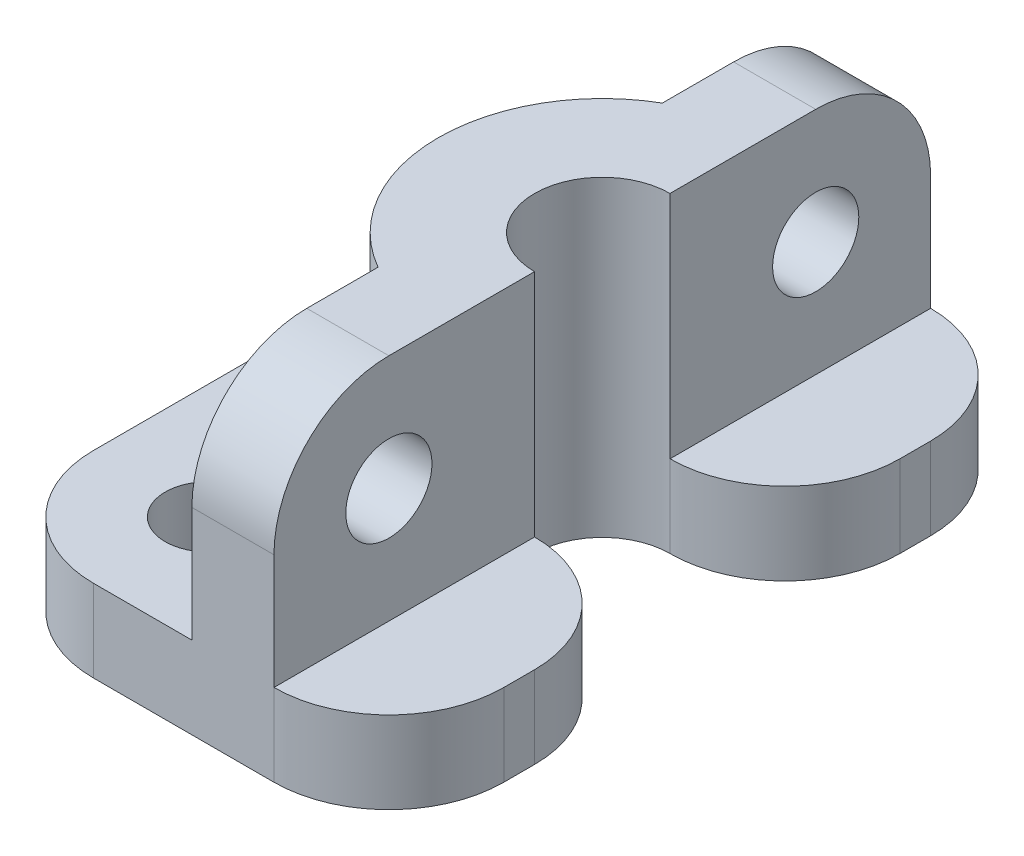
SolidWorks part; units mm, degrees
material "ABS"
ref_plane "Front Plane" through (0, 0, 0) normal (0, 0, 1) x (1, 0, 0)
ref_plane "Top Plane" through (0, 0, 0) normal (0, 1, 0) x (1, 0, 0)
ref_plane "Right Plane" through (0, 0, 0) normal (1, 0, 0) x (0, 0, -1)
sketch "Sketch1" plane through (0, 0, 0) normal (0, 1, 0) x (1, 0, 0)
  line L1 (-9, 20) -> (9, 20)
  line L2 (-9, 20) -> (-9, -20)
  line L3 (-9, -20) -> (9, -20)
  line L4 (9, 20) -> (9, -20)
  line L5 (-9, 20) -> (9, -20) construction
  line L6 (-9, -20) -> (9, 20) construction
  point P0 (0, 0)
  dimension "D1" = 18
  dimension "D2" = 40
extrude "Boss-Extrude1" add sketch "Sketch1" along normal blind 5
ref_axis "Axis1" through (9, 5, 0) along (0, 1, 0)
sketch "Sketch2" plane through (0, 5, 0) normal (0, 1, 0) x (1, 0, 0)
  line L0 (4, -20) -> (4, -8.6603)
  line L1 (-9, -20) -> (9, -20) construction
  line L2 (4, 20) -> (4, 8.6603)
  line L3 (9, 20) -> (-9, 20) construction
  line L4 (9, -20) -> (9, 20) construction
  line L9 (9, -20) -> (9, 20)
  line L10 (9, 20) -> (-9, 20)
  line L11 (-9, 20) -> (-9, -20)
  line L12 (-9, -20) -> (9, -20)
  line L13 (9, -20) -> (9, 20)
  line L14 (9, 20) -> (4, 20)
  line L16 (4, -20) -> (9, -20)
  arc A0 (4, 8.6603) -> (4, -8.6603) centre (9, 0) ccw
  dimension "D2" = 10
  dimension "D1" = 5
  dimension "D3" = 0
extrude "Boss-Extrude2" add sketch "Sketch2" along normal blind 14
sketch "Sketch3" plane through (0, 19, 0) normal (0, 1, 0) x (1, 0, 0)
  line L0 (9, -20) -> (9, 20) construction
  circle A0 centre (9, 0) radius 4.125
  dimension "D1" = 8.25
extrude "Cut-Extrude1" cut sketch "Sketch3" against normal through all
fillet "Fillet1" radius 7 2 edges at (6.5, 19, 20) (6.5, 19, -20)
sketch "Sketch6" plane through (9, 0, 0) normal (1, 0, 0) x (0, 0, -1)
  line L0 (-13, 19) -> (-4.125, 19) construction
  line L1 (-20, 12) -> (-20, 0) construction
  line L2 (0, 0) -> (0, 28.0134) construction
  circle A0 centre (-13, 12) radius 2.625
  circle A1 centre (13, 12) radius 2.625
  dimension "D1" = 5.25
  dimension "D2" = 7
  dimension "D3" = 7
extrude "Cut-Extrude3" cut sketch "Sketch6" against normal through all
sketch "Sketch7" plane through (9, 0, 0) normal (1, 0, 0) x (0, 0, -1)
  line L0 (-4.125, 0) -> (-4.125, 19) construction
  line L1 (-20, 0) -> (-4.125, 0)
  line L2 (-20, 0) -> (-20, 5)
  line L3 (-20, 5) -> (-4.125, 5)
  line L4 (-4.125, 0) -> (-4.125, 5)
  line L5 (0, 0) -> (0, 22.2367) construction
  line L6 (4.125, 0) -> (4.125, 5)
  line L7 (20, 5) -> (4.125, 5)
  line L8 (20, 0) -> (20, 5)
  line L9 (20, 0) -> (4.125, 0)
extrude "Boss-Extrude3" add sketch "Sketch7" along normal blind 7
fillet "Fillet2" radius 7 6 edges at (-9, 2.5, -20) (16, 2.5, -20) (16, 2.5, 20) (-9, 2.5, 20) (16, 2.5, -4.125) (16, 2.5, 4.125)
sketch "Sketch8" plane through (0, 5, 0) normal (0, 1, 0) x (1, 0, 0)
  line L0 (0, 0) -> (-13.0298, 0) construction
  circle A0 centre (-2, 13) radius 2.625
  circle A1 centre (-2, -13) radius 2.625
  dimension "D1" = 5.25
extrude "Cut-Extrude4" cut sketch "Sketch8" against normal through all
sketch "Sketch9" plane through (0, 0, 0) normal (0, 0, 1) x (1, 0, 0)
  line L0 (-9, 5) -> (2, 16)
  line L1 (2, 16) -> (2, 5)
  line L2 (-2, 5) -> (4, 5) construction
  line L3 (2, 5) -> (-9, 5)
  dimension "D1" = 45
  dimension "D2" = 11
extrude "Boss-Extrude4" add sketch "Sketch9" along normal blind 2.5 and the other way blind 2.5
